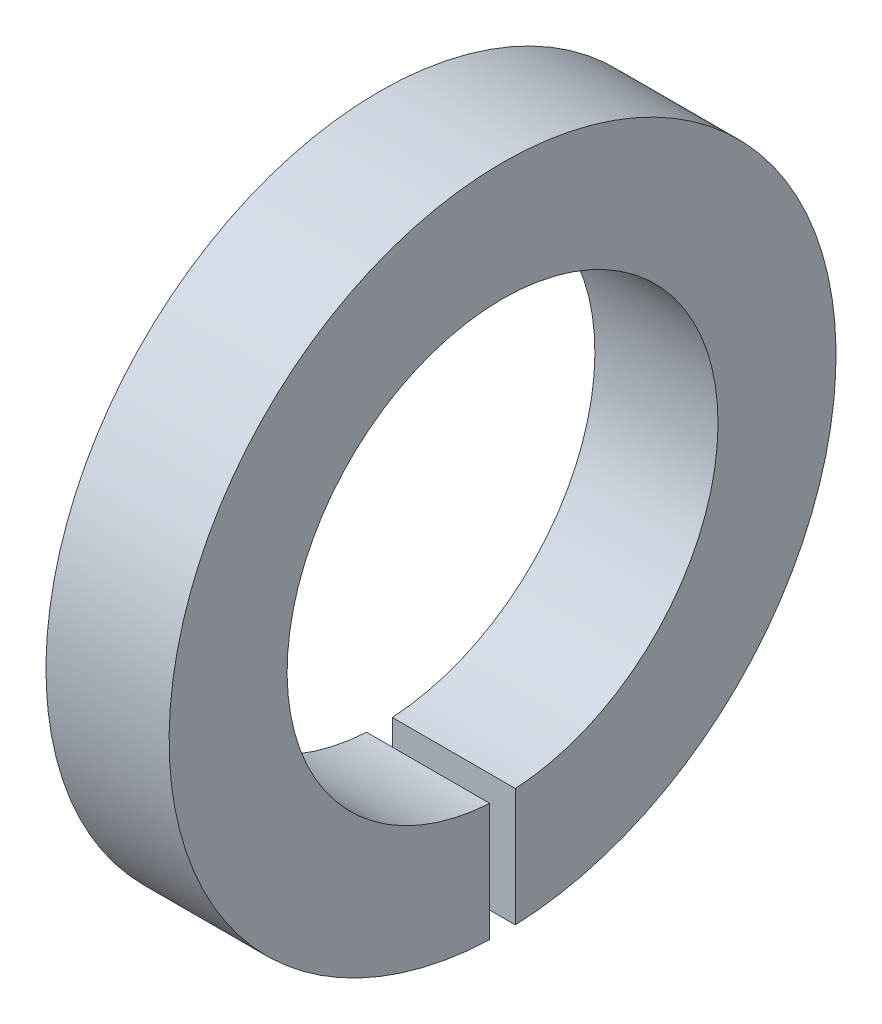
SolidWorks part; units mm, degrees
material "Cast Alloy Steel"
ref_plane "Right" through (0, 0, 0) normal (0, 0, 1) x (1, 0, 0)
ref_plane "Top" through (0, 0, 0) normal (0, 1, 0) x (1, 0, 0)
ref_plane "Front" through (0, 0, 0) normal (1, 0, 0) x (0, 0, -1)
other "Configuration Table"
sketch "Sketch1" plane through (0, 0, 0) normal (1, 0, 0) x (0, 0, -1)
  circle A0 centre (0, 0) radius 2.1
  circle A1 centre (0, 0) radius 3.25
  dimension "Insid_dia" = 4.2
  dimension "OutsideDia" = 6.5
extrude "Base-Extrude" add sketch "Sketch1" along normal blind 1.2
sketch "Sketch2" plane through (0, 0, 0) normal (1, 0, 0) x (0, 0, -1)
  line L0 (0, 0) -> (0, -3.275) construction
  line L2 (-0.125, -2.0963) -> (-0.125, -3.2476)
  line L4 (0.125, -2.0963) -> (0.125, -3.2476)
  line L5 (-0.125, -2.0963) -> (0.125, -3.2476) construction
  line L6 (-0.125, -3.2476) -> (0.125, -2.0963) construction
  circle A0 centre (0, 0) radius 2.1 construction
  circle A1 centre (0, 0) radius 3.25 construction
  arc A4 (-0.125, -2.0963) -> (0.125, -2.0963) centre (0, 0) ccw
  arc A5 (-0.125, -3.2476) -> (0.125, -3.2476) centre (0, 0) ccw
  point P5 (0, -2.6719)
  dimension "D1" = 0.25
extrude "Slit-bend" cut sketch "Sketch2" along normal through all
ref_axis "Axis-Fastener" through (4.9421, 0, 0) along (-1, 0, 0)
